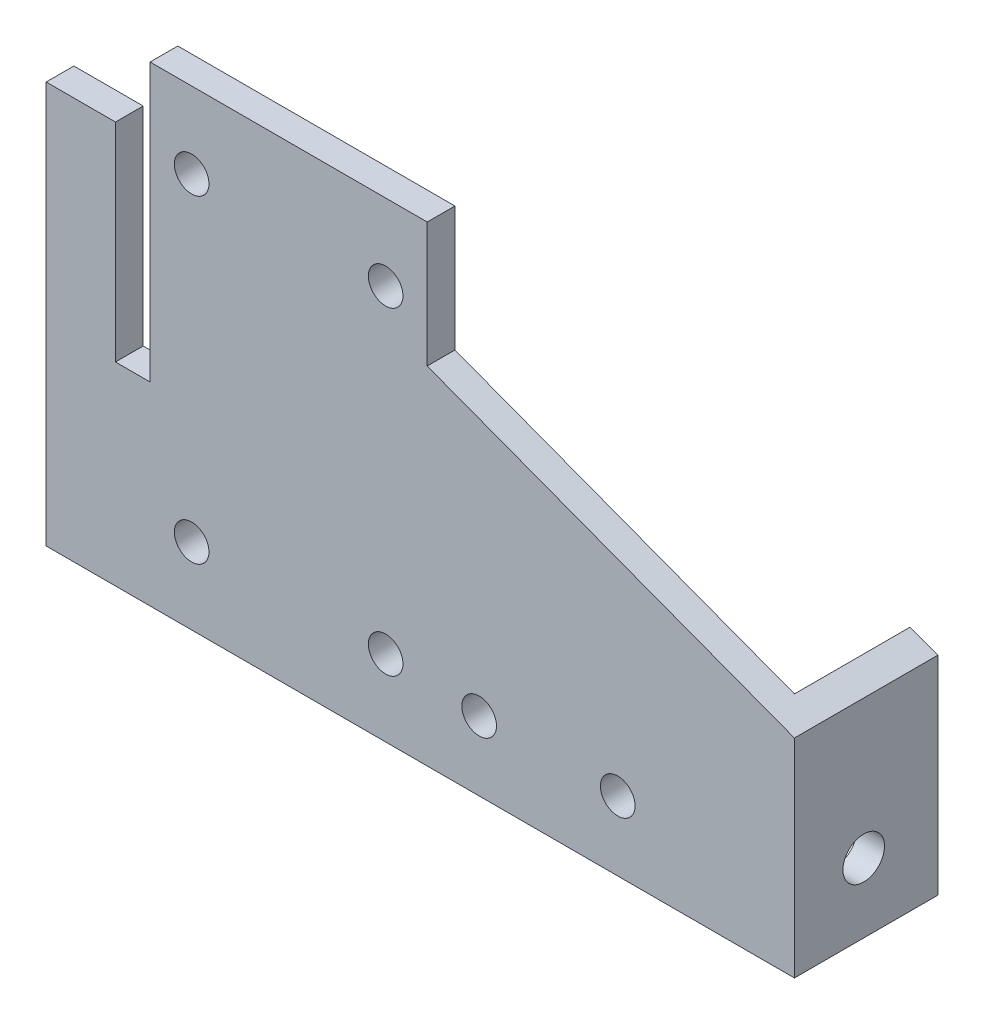
SolidWorks part; units mm, degrees
ref_plane "Спереди" through (0, 0, 0) normal (0, 0, 1) x (1, 0, 0)
ref_plane "Сверху" through (0, 0, 0) normal (0, 1, 0) x (1, 0, 0)
ref_plane "Справа" through (0, 0, 0) normal (1, 0, 0) x (0, 0, -1)
sketch "Эскиз1" plane through (0, 0, 0) normal (0, 0, 1) x (1, 0, 0)
  line L0 (35, 68) -> (35, 0) construction
  line L1 (0, 0) -> (108, 0)
  line L2 (0, 0) -> (0, 68)
  line L3 (0, 68) -> (55, 68)
  line L4 (108, 0) -> (108, 30)
  line L5 (21, 68) -> (21, 0) construction
  line L6 (55, 68) -> (55, 50)
  line L7 (59.179, 10) -> (93.8552, 10) construction
  line L8 (49, 68) -> (49, 0) construction
  line L10 (108, 30) -> (55, 50)
  circle A0 centre (21, 57) radius 2.5
  circle A1 centre (49, 57) radius 2.5
  circle A2 centre (21, 11) radius 2.5
  circle A3 centre (49, 11) radius 2.5
  circle A4 centre (82.5, 10) radius 2.5
  circle A5 centre (62.5, 10) radius 2.5
  dimension "D8" = 5
  dimension "D9" = 5
  dimension "D10" = 5
  dimension "D11" = 5
  dimension "D18" = 5
  dimension "D20" = 20
  dimension "D1" = 108
  dimension "D2" = 68
  dimension "D3" = 53
  dimension "D4" = 30
  dimension "D5" = 20
  dimension "D6" = 14
  dimension "D7" = 14
  dimension "D12" = 46
  dimension "D13" = 46
  dimension "D14" = 11
  dimension "D15" = 11
  dimension "D16" = 20
  dimension "D17" = 10
  dimension "D19" = 25.5
extrude "Бобышка-Вытянуть1" add sketch "Эскиз1" along normal blind 4
sketch "Эскиз2" plane through (0, 0, 4) normal (0, 0, 1) x (1, 0, 0)
  line L1 (108, 0) -> (104, 0)
  line L2 (0, 0) -> (108, 0) construction
  line L3 (104, 0) -> (104, 31.5094)
  line L4 (108, 30) -> (55, 50) construction
  line L5 (104, 31.5094) -> (108, 30)
  line L6 (108, 30) -> (108, 0)
  dimension "D1" = 4
extrude "Бобышка-Вытянуть2" add sketch "Эскиз2" against normal blind 20.7
sketch "Эскиз3" plane through (108, 0, 0) normal (1, 0, 0) x (0, 0, -1)
  line L2 (-4, 0) -> (-4, 30) construction
  line L4 (-4, 0) -> (16.7, 0) construction
  circle A0 centre (6, 10) radius 3
  dimension "D1" = 6
  dimension "D2" = 10
  dimension "D3" = 10
extrude "Вырез-Вытянуть1" cut sketch "Эскиз3" against normal blind 6.7
sketch "Эскиз4" plane through (0, 0, 0) normal (0, 0, -1) x (-1, 0, 0)
  line L1 (0, 68) -> (-15, 68)
  line L2 (0, 68) -> (0, 58)
  line L3 (0, 58) -> (-10, 58)
  line L4 (-15, 68) -> (-15, 48)
  line L6 (-15, 48) -> (-15, 28)
  line L7 (-15, 28) -> (-10, 28)
  line L8 (-10, 58) -> (-10, 28)
  dimension "D1" = 10
  dimension "D2" = 10
  dimension "D3" = 40
  dimension "D4" = 5
extrude "Вырез-Вытянуть2" cut sketch "Эскиз4" against normal blind 10
